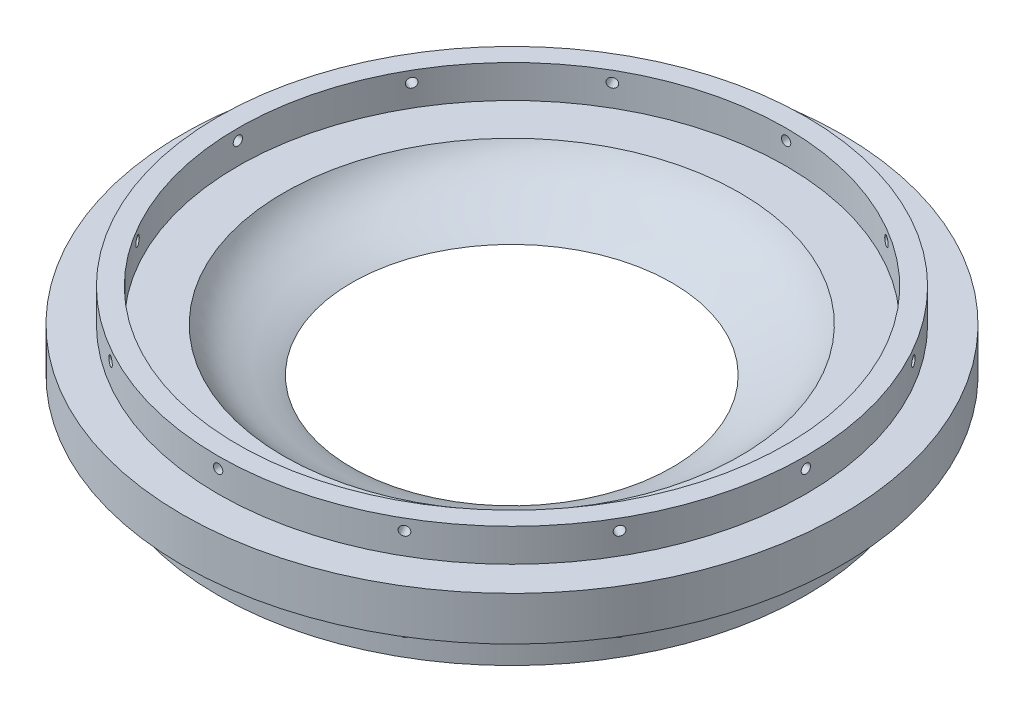
SolidWorks part; units mm, degrees
material "6061-T6 (SS)"
ref_plane "Front Plane" through (0, 0, 0) normal (0, 0, 1) x (1, 0, 0)
ref_plane "Top Plane" through (0, 0, 0) normal (0, 1, 0) x (1, 0, 0)
ref_plane "Right Plane" through (0, 0, 0) normal (1, 0, 0) x (0, 0, -1)
sketch "Sketch1" plane through (0, 0, 0) normal (0, 1, 0) x (1, 0, 0)
  line L5 (0, 0) -> (127.635, 0)
  line L6 (0, 0) -> (0, 127.635)
  line L7 (0, 127.635) -> (127.635, 127.635)
  line L8 (127.635, 0) -> (127.635, 127.635)
  dimension "D1" = 127.635
  dimension "D2" = 127.635
extrude "Boss-Extrude1" add sketch "Sketch1" along normal blind 12.7 contours L5 L8 L7 L6
sketch "Sketch12" plane through (0, 0, 0) normal (0, -1, 0) x (1, 0, 0)
  line L0 (63.8175, 0) -> (63.8175, -127.635) construction
  line L1 (0, 0) -> (127.635, 0) construction
  line L2 (0, -127.635) -> (127.635, -127.635) construction
  line L3 (0, -63.8175) -> (127.635, -63.8175) construction
  line L4 (0, 0) -> (0, -127.635) construction
  line L5 (127.635, 0) -> (127.635, -127.635) construction
  circle A0 centre (63.8175, -63.8175) radius 95.4151
  dimension "D1" = 190.8302
extrude "Boss-Extrude2" add sketch "Sketch12" against normal up to surface (12.7 mm away) contours A0 up to face at (63.8175, 12.7, -63.8175)
sketch "Sketch5" plane through (0, 12.7, 0) normal (0, 1, 0) x (1, 0, 0)
  circle A0 centre (63.8175, 63.8175) radius 46.355
  circle A3 centre (63.8175, 63.8175) radius 95.4151 construction
  dimension "D1" = 92.71
extrude "Cut-Extrude1" cut sketch "Sketch5" against normal blind 9.525
sketch "Sketch14" plane through (0, 12.7, 0) normal (0, -1, 0) x (1, 0, 0)
  line L0 (63.8175, -63.8175) -> (147.6375, -63.8175) construction
  line L1 (0, -19.2087) -> (0, 19.2087) construction
  line L2 (147.6375, -63.8175) -> (152.7175, -63.8175)
  line L3 (136.3808, -105.7742) -> (140.8401, -108.2104)
  circle A0 centre (63.8175, -63.8175) radius 46.355 construction
  arc A2 (147.6375, -63.8175) -> (136.3808, -105.7742) centre (63.8175, -63.8175) cw
  arc A3 (152.7175, -63.8175) -> (140.8401, -108.2104) centre (63.8175, -63.8175) cw
  point P0 (63.8175, -63.8175)
  dimension "D1" = 83.82
  dimension "D2" = 88.9
  dimension "D3" = 46.482
  dimension "D4" = 43.942
ref_plane "Support mirror reference plane" through (0, 4.7625, 0) normal (0, 1, 0) x (1, 0, 0)
sketch "Sketch25" plane through (0, 12.7, 0) normal (0, -1, 0) x (1, 0, 0)
  line L0 (63.8175, -63.8175) -> (123.0872, -4.5478) construction
  line L2 (123.0872, -4.5478) -> (126.6793, -0.9557)
  line L3 (144.7953, -42.1754) -> (149.6712, -40.7448)
  line L5 (63.8175, -63.8175) -> (147.6375, -63.8175) construction
  arc A2 (123.0872, -4.5478) -> (144.7953, -42.1754) centre (63.8175, -63.8175) cw
  arc A3 (126.6793, -0.9557) -> (149.6712, -40.7448) centre (63.8175, -63.8175) cw
  point P0 (63.8175, -63.8175)
  dimension "D1" = 83.82
  dimension "D2" = 88.9
  dimension "D3" = 46.482
  dimension "D4" = 43.942
  dimension "D5" = 45
sketch "Sketch30" plane through (0, 0, 0) normal (0, -1, 0) x (1, 0, 0)
  circle A0 centre (63.8175, -63.8175) radius 85.09
  circle A1 centre (63.8175, -63.8175) radius 79.375
  dimension "D1" = 170.18
  dimension "D2" = 158.75
extrude "Boss-Extrude3" add sketch "Sketch30" along normal blind 12.7
mirror "Mirror1" about plane through (0, 4.7625, 0) normal (0, 1, 0) of "Boss-Extrude3"
sketch "Sketch31" plane through (0, 0, 0) normal (0, -1, 0) x (-1, 0, 0)
  line L0 (-63.8175, -52.481) -> (-63.8175, 177.7216) construction
ref_plane "Plane1" through (0, 0, -148.9075) normal (0, 0, -1) x (-1, 0, 0)
ref_plane "Plane2" through (63.8175, 0, 0) normal (-1, 0, 0) x (0, 0, -1)
sketch "Sketch32" plane through (0, 0, -148.9075) normal (0, 0, -1) x (-1, 0, 0)
  line L4 (-63.8175, -87.3125) -> (-63.8175, 87.3125) construction
  line L5 (-148.9075, 0) -> (21.2725, 0) construction
  line L6 (21.2725, 12.7) -> (-148.9075, 12.7) construction
  circle A0 centre (-63.8175, -6.35) radius 1.3526
  circle A1 centre (-63.8175, 19.05) radius 1.3525
  dimension "D1" = 2.7051
  dimension "D2" = 2.7051
  dimension "D3" = 6.35
  dimension "D4" = 6.35
extrude "Cut-Extrude4" cut sketch "Sketch32" against normal blind 15.24
pattern_circular "CirPattern2" count 12 over 360 about axis through (63.8175, -12.7, -63.8175) along (0, 1, 0) of "Cut-Extrude4"
ref_plane "Plane3" through (0, 0, -63.754) normal (0, 0, 1) x (1, 0, 0)
sketch "Sketch35" plane through (0, 0, -63.754) normal (0, 0, 1) x (1, 0, 0)
  line L3 (110.1725, 12.7) -> (17.4625, 12.7) construction
  line L4 (63.8175, 12.7) -> (129.8575, 12.7)
  line L6 (63.8175, -10.3302) -> (63.8175, 21.6129) construction
  line L8 (110.1725, 0) -> (63.8175, 0)
  line L9 (63.8175, 0) -> (63.8175, 12.7)
  circle A0 centre (63.8175, 19.05) radius 1.3526 construction
  circle A1 centre (63.8175, 19.05) radius 1.3525
  spline S0 degree 3 poles (129.8575, 12.7) (125.5567, 5.3002) (116.9453, 3.9994) (110.1725, 0) knots 0 0 0 0 1 1 1 1
  point P1 (0, 0)
  point P12 (0, 0)
  point P14 (114.1214, 2.0166)
  dimension "D1" = 12.7
  dimension "D2" = 46.355
  dimension "D3" = 66.04
revolve "Cut-Revolve1" cut sketch "Sketch35" angle 360 about L6 region at (93.1982, 6.7257, -63.754)
